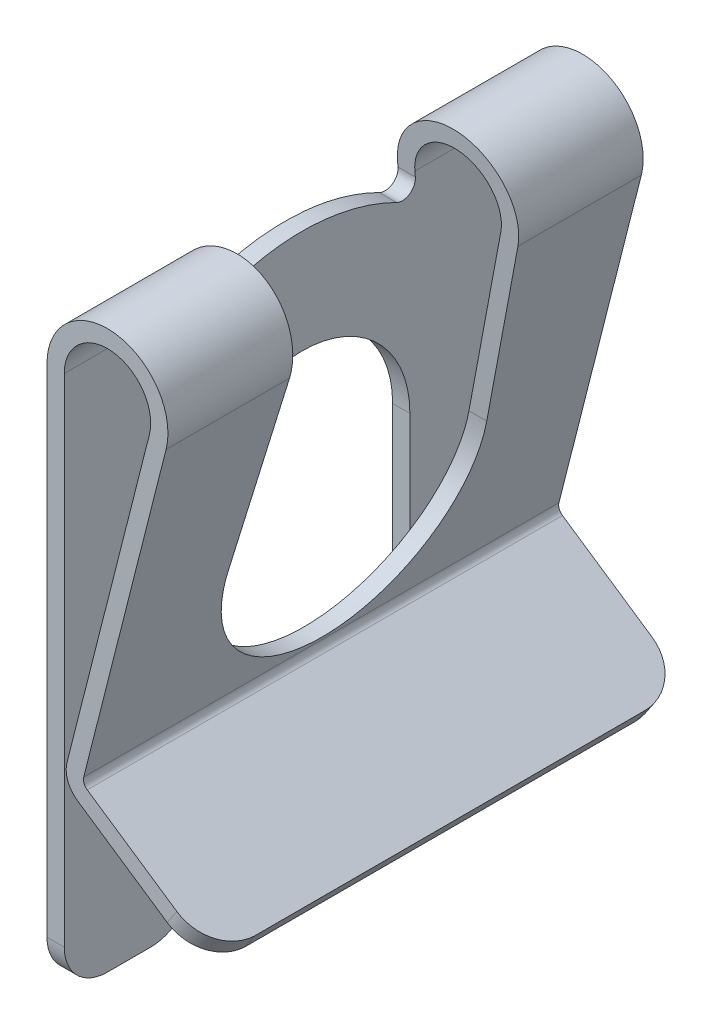
SolidWorks part; units mm, degrees
ref_plane "Front Plane" through (0, 0, 0) normal (0, 0, 1) x (1, 0, 0)
ref_plane "Top Plane" through (0, 0, 0) normal (0, 1, 0) x (1, 0, 0)
ref_plane "Right Plane" through (0, 0, 0) normal (1, 0, 0) x (0, 0, -1)
ref_plane "Plane1" through (0, 0, 0) normal (0, 0, 1) x (1, 0, 0)
sketch "Sketch1" plane through (0, 0, 0) normal (0, 0, 1) x (1, 0, 0)
  line L0 (0, 4.8) -> (0, -7.7)
  line L1 (0, -7.7) -> (0.4, -7.7)
  line L2 (0.4, -7.7) -> (0.4, 4.8)
  line L3 (2.3693, 4.5542) -> (0.4621, -2.9672)
  line L4 (0.7079, -3.6119) -> (3.6112, -5.573)
  line L5 (3.6112, -5.573) -> (3.8351, -5.2416)
  line L6 (3.8351, -5.2416) -> (0.9318, -3.2804)
  line L7 (0.8499, -3.0655) -> (2.7571, 4.4559)
  arc A0 (0.4, 4.8) -> (2.3693, 4.5542) centre (1.4, 4.8) cw
  arc A1 (0.4621, -2.9672) -> (0.7079, -3.6119) centre (1.0437, -3.1147) ccw
  arc A2 (0.9318, -3.2804) -> (0.8499, -3.0655) centre (1.0437, -3.1147) cw
  arc A3 (2.7571, 4.4559) -> (0, 4.8) centre (1.4, 4.8) ccw
extrude "Boss-Extrude1" add sketch "Sketch1" against normal blind 5.5 and the other way blind 5.5
ref_plane "Plane2" through (0, 0, 0) normal (1, 0, 0) x (0, 0, -1)
sketch "Sketch2" plane through (0, 0, 0) normal (1, 0, 0) x (0, 0, -1)
  line L0 (-2.5, 0) -> (-2.5, -7.7)
  line L1 (-2.5, -7.7) -> (2.5, -7.7)
  line L2 (2.5, -7.7) -> (2.5, 0)
  arc A0 (2.5, 0) -> (-2.5, 0) centre (0, 0) ccw
extrude "Cut-Extrude1" cut sketch "Sketch2" along normal blind 0.4
ref_plane "Plane3" through (0.4, 0, 0) normal (1, 0, 0) x (0, 0, -1)
sketch "Sketch3" plane through (0.4, 0, 0) normal (1, 0, 0) x (0, 0, -1)
  line L0 (2.9899, 0.246) -> (2.5, 6.2)
  line L1 (2.5, 6.2) -> (-2.5, 6.2)
  line L2 (-2.5, 6.2) -> (-2.9899, 0.246)
  arc A0 (-2.9899, 0.246) -> (2.9899, 0.246) centre (0, 0) ccw
extrude "Cut-Extrude2" cut sketch "Sketch3" along normal blind 3.8
ref_plane "Plane4" through (0.4, 0, 0) normal (1, 0, 0) x (0, 0, -1)
sketch "Sketch4" plane through (0.4, 0, 0) normal (1, 0, 0) x (0, 0, -1)
  line L0 (2.6255, 4.6751) -> (2.5, 6.2)
  line L1 (2.5, 6.2) -> (-2.5, 6.2)
  line L2 (-2.5, 6.2) -> (-2.6255, 4.6751)
  arc A0 (-2.6255, 4.6751) -> (-2.1923, 4.3822) centre (-2.3265, 4.6505) ccw
  arc A1 (-2.1923, 4.3822) -> (2.1923, 4.3822) centre (0, 0) cw
  arc A2 (2.1923, 4.3822) -> (2.6255, 4.6751) centre (2.3265, 4.6505) ccw
extrude "Cut-Extrude3" cut sketch "Sketch4" against normal blind 3.8
ref_plane "Plane5" through (0, 0, 0) normal (1, 0, 0) x (0, 0, -1)
sketch "Sketch5" plane through (0, 0, 0) normal (1, 0, 0) x (0, 0, -1)
  line L0 (-5.5, -7.7) -> (-4.5, -7.7)
  line L1 (-5.5, -6.7) -> (-5.5, -7.7)
  arc A0 (-4.5, -7.7) -> (-5.5, -6.7) centre (-4.5, -6.7) cw
extrude "Cut-Extrude4" cut sketch "Sketch5" along normal blind 0.4
ref_plane "Plane6" through (0, 0, 0) normal (1, 0, 0) x (0, 0, -1)
sketch "Sketch6" plane through (0, 0, 0) normal (1, 0, 0) x (0, 0, -1)
  line L0 (4.5, -7.7) -> (5.5, -7.7)
  line L1 (5.5, -7.7) -> (5.5, -6.7)
  arc A0 (5.5, -6.7) -> (4.5, -7.7) centre (4.5, -6.7) cw
extrude "Cut-Extrude5" cut sketch "Sketch6" along normal blind 0.4
ref_plane "Plane7" through (0, 0, 0) normal (1, 0, 0) x (0, 0, -1)
sketch "Sketch7" plane through (0, 0, 0) normal (1, 0, 0) x (0, 0, -1)
  line L0 (2.5, -7.7) -> (3.5, -7.7)
  line L1 (2.5, -6.7) -> (2.5, -7.7)
  arc A0 (3.5, -7.7) -> (2.5, -6.7) centre (3.5, -6.7) cw
extrude "Cut-Extrude6" cut sketch "Sketch7" along normal blind 0.4
ref_plane "Plane8" through (0, 0, 0) normal (1, 0, 0) x (0, 0, -1)
sketch "Sketch8" plane through (0, 0, 0) normal (1, 0, 0) x (0, 0, -1)
  line L0 (-3.5, -7.7) -> (-2.5, -7.7)
  line L1 (-2.5, -7.7) -> (-2.5, -6.7)
  arc A0 (-2.5, -6.7) -> (-3.5, -7.7) centre (-3.5, -6.7) cw
extrude "Cut-Extrude7" cut sketch "Sketch8" along normal blind 0.4
ref_plane "Plane9" through (-1.2297, -1.8204, 0) normal (0.5597, 0.8287, 0) x (0.8287, -0.5597, 0)
sketch "Sketch9" plane through (-1.2297, -1.8204, 0) normal (0.5597, 0.8287, 0) x (0.8287, -0.5597, 0)
  line L0 (6.1123, 4.5) -> (6.1123, -4.5)
  line L1 (5.1123, -5.5) -> (5.1123, -6.5)
  line L2 (5.1123, -6.5) -> (7.1123, -6.5)
  line L3 (7.1123, -6.5) -> (7.1123, 6.5)
  line L4 (7.1123, 6.5) -> (5.1123, 6.5)
  line L5 (5.1123, 6.5) -> (5.1123, 5.5)
  arc A0 (5.1123, 5.5) -> (6.1123, 4.5) centre (5.1123, 4.5) cw
  arc A1 (6.1123, -4.5) -> (5.1123, -5.5) centre (5.1123, -4.5) cw
extrude "Cut-Extrude8" cut sketch "Sketch9" against normal blind 0.8 and the other way blind 0.8
